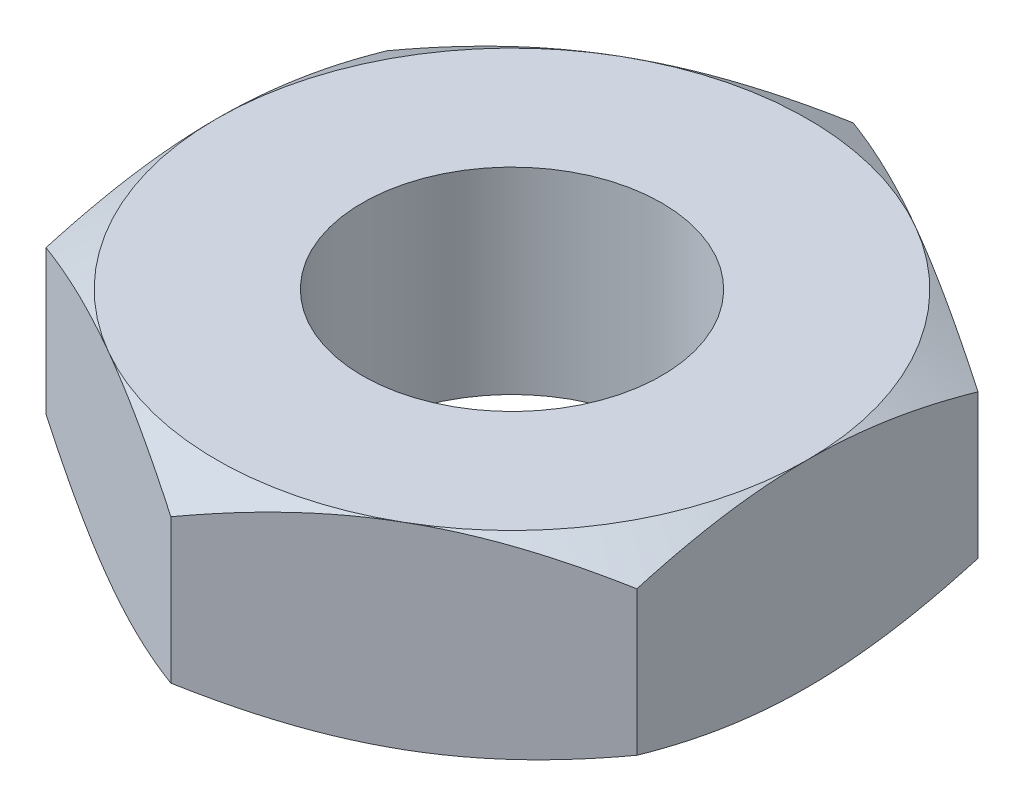
SolidWorks part; units mm, degrees
material "Plain Carbon Steel"
ref_plane "Front Plane" through (0, 0, 0) normal (0, 0, 1) x (1, 0, 0)
ref_plane "Top Plane" through (0, 0, 0) normal (0, 1, 0) x (1, 0, 0)
ref_plane "Right Plane" through (0, 0, 0) normal (1, 0, 0) x (0, 0, -1)
sketch "Sketch7" plane through (0, 0, 0) normal (0, 1, 0) x (1, 0, 0)
  line L0 (-4.7625, 0) -> (4.7625, 0) construction
  line L1 (-2.413, 0) -> (2.413, 0) construction
  line L2 (-4.7625, 0) -> (-4.7625, -1.0583) construction
  point P4 (0, 0)
  point P8 (0, 0)
sketch "Sketch6" plane through (0, 0, 0) normal (1, 0, 0) x (0, 0, -1)
  line L0 (0, 1.5875) -> (0, -1.5875) construction
  point P4 (0, 0)
sketch "Sketch1" plane through (0, 0, 0) normal (0, 1, 0) x (1, 0, 0)
  line L1 (-4.7625, 2.7496) -> (-4.7625, -2.7496)
  line L2 (-4.7625, -2.7496) -> (0, -5.4993)
  line L3 (0, -5.4993) -> (4.7625, -2.7496)
  line L4 (4.7625, -2.7496) -> (4.7625, 2.7496)
  line L5 (4.7625, 2.7496) -> (0, 5.4993)
  line L6 (0, 5.4993) -> (-4.7625, 2.7496)
  circle A0 centre (0, 0) radius 4.7625 construction
  circle A1 centre (0, 0) radius 2.413
extrude "Boss-Extrude1" add sketch "Sketch1" along normal mid plane 3.175
sketch "Sketch5" plane through (0, 1.5875, 0) normal (0, 1, 0) x (1, 0, 0)
  circle A0 centre (0, 0) radius 4.7625 construction
  circle A1 centre (0, 0) radius 4.7625
extrude "Cut-Extrude2" cut sketch "Sketch5" against normal through all draft 60 flip side to cut
mirror "Mirror1" about plane through (0, 0, 0) normal (0, 1, 0) of "Cut-Extrude2"
sketch "Sketch14" plane through (0, 1.5875, 0) normal (0, 1, 0) x (1, 0, 0)
  line L0 (-2.413, 0) -> (2.413, 0) construction
  line L1 (0, 2.413) -> (0, -2.413) construction
  circle A0 centre (0, 0) radius 2.413 construction
  point P7 (0, 0)
  point P11 (0, 0)
  point P12 (0, -2.413)
  point P13 (-2.413, 0)
  point P14 (0, 2.413)
  point P15 (2.413, 0)
sketch "Sketch8" [suppressed] plane through (0, 1.5875, 0) normal (0, 1, 0) x (1, 0, 0)
  circle A0 centre (0, 0) radius 2.413 construction
  circle A1 centre (0, 0) radius 2.413
extrude "Boss-Extrude2" [suppressed] add sketch "Sketch8" against normal up to surface (3.175 mm away) separate body
sketch "Sketch9" [suppressed] plane through (0, 1.5875, 0) normal (0, 1, 0) x (1, 0, 0)
  circle A0 centre (0, 0) radius 2.413 construction
  circle A1 centre (0, 0) radius 2.413
extrude "Boss-Extrude3" [suppressed] add sketch "Sketch9" against normal up to surface (3.175 mm away)
sketch "Sketch10" [suppressed] plane through (0, 1.5875, 0) normal (0, 1, 0) x (1, 0, 0)
  circle A0 centre (0, 0) radius 2.413 construction
  circle A1 centre (0, 0) radius 2.413
curve "Helix/Spiral1" [suppressed] pitch 1.0583 height 4.2333 turns 4
sketch "Sketch11" [suppressed] plane through (0, 0, 0) normal (1, 0, 0) x (0, 0, -1)
  line L0 (-2.413, 1.5875) -> (-2.413, 2.5135)
  line L1 (2.413, 1.5875) -> (-2.413, 1.5875) construction
  line L2 (-2.413, 2.5135) -> (-1.7256, 2.1167)
  line L3 (-1.7256, 2.1167) -> (-1.7256, 1.9844)
  line L4 (-1.7256, 1.9844) -> (-2.413, 1.5875)
  line L5 (-2.413, 2.0505) -> (-1.7256, 2.0505) construction
  line L6 (-2.0693, 2.3151) -> (-2.0693, 1.7859) construction
  spline S0 degree 3 poles (-2.413, 1.5875) (-2.413, 1.5652) (-2.2833, 1.5202) (-1.7301, 1.4531) (-0.9053, 1.3859) (0.0618, 1.3187) (1.0191, 1.2515) (1.8164, 1.1843) (2.3284, 1.1171) (2.4748, 1.0499) (2.2325, 0.9827) (1.6396, 0.9155) (0.7892, 0.8483) (-0.1852, 0.7812) (-1.1304, 0.714) (-1.8981, 0.6468) (-2.3678, 0.5796) (-2.4655, 0.5124) (-2.1761, 0.4452) (-1.5449, 0.378) (-0.6711, 0.3108) (0.3081, 0.2436) (1.2389, 0.1764) (1.9752, 0.1092) (2.4012, 0.042) (2.4502, -0.0252) (2.1143, -0.0924) (1.4464, -0.1596) (0.5514, -0.2268) (-0.4303, -0.294) (-1.3444, -0.3612) (-2.0473, -0.4284) (-2.4287, -0.4956) (-2.4287, -0.5628) (-2.0473, -0.63) (-1.3444, -0.6972) (-0.4303, -0.7644) (0.5514, -0.8315) (1.4464, -0.8987) (2.1143, -0.9659) (2.4502, -1.0331) (2.4012, -1.1003) (1.9752, -1.1675) (1.2389, -1.2347) (0.3081, -1.3019) (-0.6711, -1.3691) (-1.5449, -1.4363) (-2.1761, -1.5035) (-2.4655, -1.5707) (-2.3678, -1.6379) (-1.8981, -1.7051) (-1.1304, -1.7723) (-0.1852, -1.8395) (0.7892, -1.9067) (1.6396, -1.9739) (2.2325, -2.0411) (2.4748, -2.1083) (2.3284, -2.1755) (1.8164, -2.2427) (1.0191, -2.3099) (0.0618, -2.3771) (-0.9053, -2.4442) (-1.7301, -2.5115) (-2.2833, -2.5786) (-2.413, -2.6236) (-2.413, -2.6458) knots 0 0 0 0 0.015873 0.031746 0.047619 0.063492 0.079365 0.095238 0.111111 0.126984 0.142857 0.15873 0.174603 0.190476 0.206349 0.222222 0.238095 0.253968 0.269841 0.285714 0.301587 0.31746 0.333333 0.349206 0.365079 0.380952 0.396825 0.412698 0.428571 0.444444 0.460317 0.47619 0.492063 0.507937 0.52381 0.539683 0.555556 0.571429 0.587302 0.603175 0.619048 0.634921 0.650794 0.666667 0.68254 0.698413 0.714286 0.730159 0.746032 0.761905 0.777778 0.793651 0.809524 0.825397 0.84127 0.857143 0.873016 0.888889 0.904762 0.920635 0.936508 0.952381 0.968254 0.984127 1 1 1 1 construction
  dimension "D1" = 60
  dimension "D2" = 0.1323
  dimension "D3" = 0.5292
sweep "Cut-Sweep1" [suppressed] cut profiles "Sketch11" path "Helix/Spiral1"
combine bodies "Combine1" [suppressed] operation type add bodies to combine 107 108
sketch "Sketch12" [suppressed] plane through (0, 1.5875, 0) normal (0, 1, 0) x (1, 0, 0)
  circle A1 centre (0, 0) radius 2.413
  circle A2 centre (0, 0) radius 2.413
  dimension "D1" = 0
extrude "Cut-Extrude3" [suppressed] cut sketch "Sketch12" against normal through all draft 45
sketch "Sketch13" [suppressed] plane through (0, -1.5875, 0) normal (0, -1, 0) x (1, 0, 0)
  circle A1 centre (0, 0) radius 2.413
  circle A2 centre (0, 0) radius 2.413
  dimension "D1" = 0
extrude "Cut-Extrude4" [suppressed] cut sketch "Sketch13" against normal through all draft 45
equation "\"D3@Helix/Spiral1\"=\"Thickness@Sketch6\"+\"Pitch@Sketch7\""
equation "\"Height@Boss-Extrude1\"=\"Thickness@Sketch6\""
equation "\"D4@Helix/Spiral1\"=\"Pitch@Sketch7\""
equation "\"D2@Sketch11\"=\"Pitch@Sketch7\"*.125"
equation "\"D3@Sketch11\"=\"Pitch@Sketch7\"*.5"
